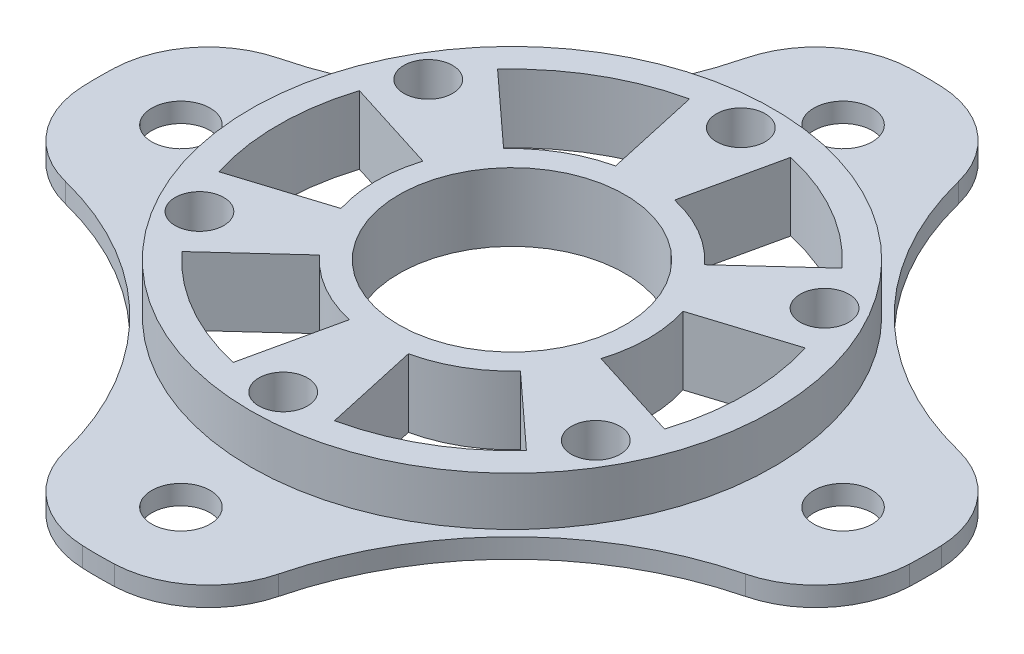
SolidWorks part; units mm, degrees
ref_plane "Front Plane" through (0, 0, 0) normal (0, 0, 1) x (1, 0, 0)
ref_plane "Top Plane" through (0, 0, 0) normal (0, 1, 0) x (1, 0, 0)
ref_plane "Right Plane" through (0, 0, 0) normal (1, 0, 0) x (0, 0, -1)
sketch "Sketch1" plane through (0, 0, 0) normal (0, 1, 0) x (1, 0, 0)
  circle A0 centre (0, 0) radius 26.85
  dimension "D1" = 53.7
extrude "Boss-Extrude1" add sketch "Sketch1" against normal blind 5
sketch "Sketch2" plane through (0, -5, 0) normal (0, -1, 0) x (1, 0, 0)
  circle A0 centre (0, 0) radius 42.5
  dimension "D1" = 85
extrude "Boss-Extrude2" add sketch "Sketch2" along normal blind 2
sketch "Sketch3" plane through (0, -5, 0) normal (0, 1, 0) x (1, 0, 0)
  circle A0 centre (0, 34) radius 3
  circle A1 centre (34, 0) radius 3
  circle A2 centre (0, -34) radius 3
  circle A3 centre (-34, 0) radius 3
  circle A4 centre (0, 0) radius 42.5 construction
  arc A5 (-10, 41.3068) -> (-41.3068, 10) centre (-42.9586, 42.9586) cw
  arc A6 (41.3068, 10) -> (10, 41.3068) centre (42.9586, 42.9586) cw
  arc A7 (10, -41.3068) -> (41.3068, -10) centre (42.9586, -42.9586) cw
  arc A8 (-41.3068, -10) -> (-10, -41.3068) centre (-42.9586, -42.9586) cw
  circle A10 centre (0, 0) radius 42.5
  circle A11 centre (0, 0) radius 42.5
  point P2 (0, 0)
  point P4 (47.6675, -9.1565)
  point P12 (0, 0)
  point P17 (0, 0)
  point P27 (0, 0)
  circle M3 centre (0, 0) radius 42.5
  dimension "D1" = 6
  dimension "D6" = 33
  dimension "D2" = 34
  dimension "D3" = 4
  dimension "D4" = 10
  dimension "D5" = 10
  dimension "D8" = 0
  dimension "D7" = 4
extrude "Cut-Extrude1" cut sketch "Sketch3" against normal blind 2 contours A5 M3 | A0 | A6 M3 | A1 | A2 | A7 M3 | A8 M3 | A3 region at (0, -5, -34) region at (34, -5, 0) region at (0, -5, 34) region at (-34, -5, 0) region at (-24.9758, -5, -24.9758) region at (24.9758, -5, -24.9758) region at (-24.9758, -5, 24.9758) region at (24.9758, -5, 24.9758)
sketch "Sketch4" plane through (0, 0, 0) normal (0, 1, 0) x (1, 0, 0)
  circle A0 centre (0, 0) radius 11.6
  circle A1 centre (0, 23.5) radius 2.5
  circle A2 centre (20.3516, 11.75) radius 2.5
  circle A3 centre (20.3516, -11.75) radius 2.5
  circle A4 centre (0, -23.5) radius 2.5
  circle A5 centre (-20.3516, -11.75) radius 2.5
  circle A6 centre (-20.3516, 11.75) radius 2.5
  point P5 (-54.1309, -6.4634)
  point P6 (0, 0)
  point P18 (0, 0)
  dimension "D1" = 23.2
  dimension "D2" = 5
  dimension "D3" = 23.5
  dimension "D4" = 6
extrude "Cut-Extrude2" cut sketch "Sketch4" against normal through all
sketch "Sketch5" plane through (0, 0, 0) normal (0, 1, 0) x (1, 0, 0)
  line L0 (-17.6947, 16.2142) -> (-10.3219, 9.4583)
  line L1 (-5.1946, 23.4311) -> (-3.0302, 13.6681)
  line L2 (0, 23.537) -> (0, 0) construction
  line L3 (17.6947, 16.2142) -> (10.3219, 9.4583)
  line L4 (5.1946, 23.4311) -> (3.0302, 13.6681)
  line L5 (22.8892, -7.2169) -> (13.352, -4.2099)
  line L6 (22.8892, 7.2169) -> (13.352, 4.2099)
  line L7 (5.1946, -23.4311) -> (3.0302, -13.6681)
  line L8 (17.6947, -16.2142) -> (10.3219, -9.4583)
  line L9 (-17.6947, -16.2142) -> (-10.3219, -9.4583)
  line L10 (-5.1946, -23.4311) -> (-3.0302, -13.6681)
  line L11 (-22.8892, 7.2169) -> (-13.352, 4.2099)
  line L12 (-22.8892, -7.2169) -> (-13.352, -4.2099)
  arc A0 (-10.3219, 9.4583) -> (-3.0302, 13.6681) centre (0, 0) cw
  arc A1 (-17.6947, 16.2142) -> (-5.1946, 23.4311) centre (0, 0) cw
  arc A2 (5.1946, 23.4311) -> (17.6947, 16.2142) centre (0, 0) cw
  arc A3 (3.0302, 13.6681) -> (10.3219, 9.4583) centre (0, 0) cw
  arc A4 (22.8892, 7.2169) -> (22.8892, -7.2169) centre (0, 0) cw
  arc A5 (13.352, 4.2099) -> (13.352, -4.2099) centre (0, 0) cw
  arc A6 (17.6947, -16.2142) -> (5.1946, -23.4311) centre (0, 0) cw
  arc A7 (10.3219, -9.4583) -> (3.0302, -13.6681) centre (0, 0) cw
  arc A8 (-5.1946, -23.4311) -> (-17.6947, -16.2142) centre (0, 0) cw
  arc A9 (-3.0302, -13.6681) -> (-10.3219, -9.4583) centre (0, 0) cw
  arc A10 (-22.8892, -7.2169) -> (-22.8892, 7.2169) centre (0, 0) cw
  arc A11 (-13.352, -4.2099) -> (-13.352, 4.2099) centre (0, 0) cw
  point P30 (0, 0)
  dimension "D2" = 14
  dimension "D3" = 35
  dimension "D4" = 12.5
  dimension "D1" = 10
  dimension "D5" = 6
extrude "Cut-Extrude3" cut sketch "Sketch5" against normal through all
fillet "Fillet1" radius 10 8 edges at (10, -6, -41.3068) (-10, -6, -41.3068) (-41.3068, -6, -10) (-41.3068, -6, 10) (10, -6, 41.3068) (-10, -6, 41.3068) (41.3068, -6, 10) (41.3068, -6, -10)
